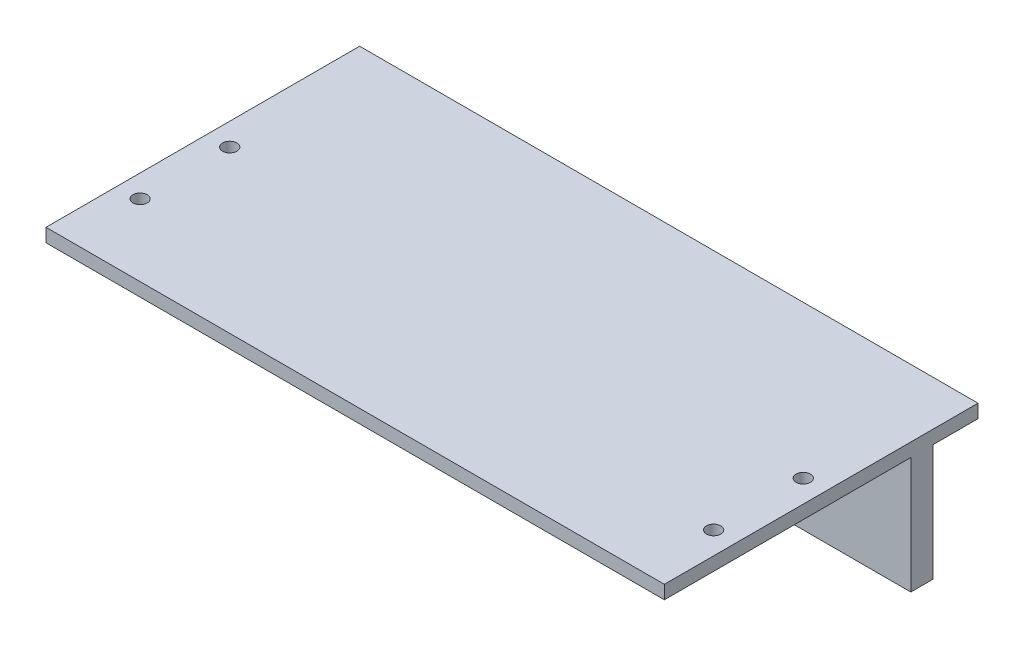
SolidWorks part; units mm, degrees
ref_plane "前视基准面" through (0, 0, 0) normal (0, 0, 1) x (1, 0, 0)
ref_plane "上视基准面" through (0, 0, 0) normal (0, 1, 0) x (1, 0, 0)
ref_plane "右视基准面" through (0, 0, 0) normal (1, 0, 0) x (0, 0, -1)
other "Configuration Table"
sketch "草图1" plane through (0, 0, 0) normal (0, 0, 1) x (1, 0, 0)
  line L0 (-49.798, -1.43) -> (88.202, -1.43) construction
  line L1 (-49.798, 14.57) -> (88.202, 14.57)
  line L2 (-49.798, 14.57) -> (-49.798, -11.43)
  line L3 (-49.798, -11.43) -> (88.202, -11.43)
  line L4 (88.202, 14.57) -> (88.202, -11.43)
  line L5 (19.202, 14.57) -> (19.202, -11.43) construction
  circle A0 centre (-29.798, -1.43) radius 2.1
  circle A1 centre (68.202, -1.43) radius 2.1
  point P12 (0, 0)
  point P13 (0, 0)
  point P14 (85.202, -1.43)
  dimension "D4" = 4.2
  dimension "D1" = 26
  dimension "D2" = 138
  dimension "D3" = 20
  dimension "D5" = 10
extrude "凸台-拉伸1" add sketch "草图1" along normal blind 5
sketch "草图2" plane through (0, 14.57, 0) normal (0, 1, 0) x (1, 0, 0)
  line L0 (88.202, -5) -> (88.202, 0) construction
  line L1 (-49.798, 10) -> (88.202, 10)
  line L2 (-49.798, 10) -> (-49.798, -60)
  line L3 (-49.798, -60) -> (88.202, -60)
  line L4 (88.202, 10) -> (88.202, -60)
  line L6 (-49.798, -5) -> (-49.798, 0) construction
  line L7 (88.202, 0) -> (-49.798, 0) construction
  line L8 (88.202, -5) -> (-49.798, -5) construction
  dimension "D1" = 10
  dimension "D2" = 55
extrude "凸台-拉伸2" add sketch "草图2" along normal blind 3
sketch "草图3" plane through (0, 17.57, 0) normal (0, 1, 0) x (1, 0, 0)
  line L0 (-44.798, -15) -> (-44.798, -60) construction
  line L1 (-49.798, -15) -> (-4.798, -15) construction
  line L2 (-49.798, -15) -> (-49.798, -60) construction
  line L3 (-49.798, -60) -> (-4.798, -60) construction
  line L4 (-4.798, -15) -> (-4.798, -60) construction
  line L5 (-49.798, -44) -> (-44.798, -44) construction
  line L6 (-49.798, -24) -> (-44.798, -24) construction
  line L7 (-49.798, -60) -> (88.202, -60) construction
  line L8 (-49.798, 10) -> (-49.798, -60) construction
  line L9 (83.202, -15) -> (83.202, -60) construction
  line L10 (88.202, -60) -> (78.202, -60) construction
  line L11 (88.202, -60) -> (88.202, -15) construction
  line L12 (88.202, -15) -> (78.202, -15) construction
  line L13 (78.202, -60) -> (78.202, -15) construction
  circle A0 centre (-44.798, -24) radius 1.6
  circle A1 centre (-44.798, -44) radius 1.6
  circle A2 centre (83.202, -24) radius 1.6
  circle A3 centre (83.202, -44) radius 1.6
  point P28 (0, 0)
  point P29 (0, 0)
  dimension "D6" = 3.2
  dimension "D9" = 3.2
  dimension "D1" = 45
  dimension "D2" = 5
  dimension "D3" = 45
  dimension "D4" = 16
  dimension "D5" = 20
  dimension "D7" = 10
  dimension "D8" = 5
extrude "切除-拉伸1" cut sketch "草图3" against normal blind 3
